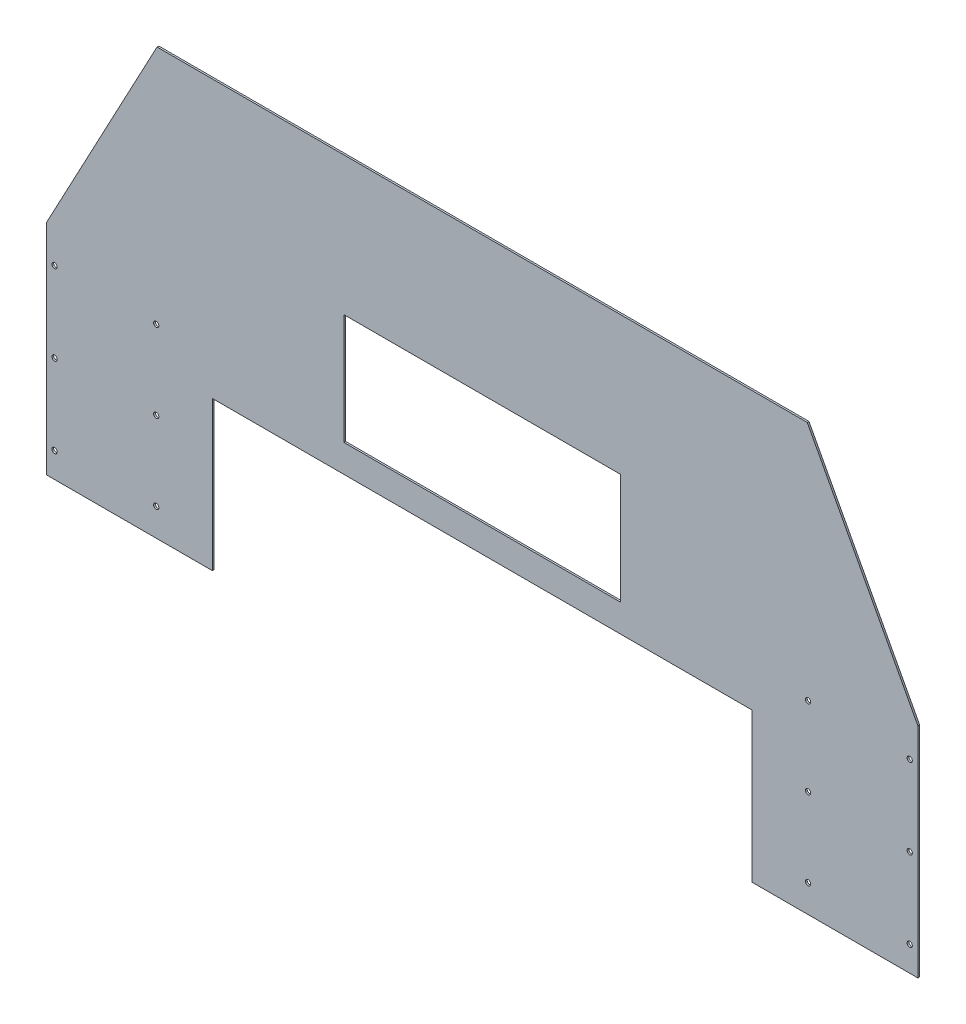
SolidWorks part; units mm, degrees
material "6061-T6 (SS)"
ref_plane "Front Plane" through (0, 0, 0) normal (0, 0, 1) x (1, 0, 0)
ref_plane "Top Plane" through (0, 0, 0) normal (0, 1, 0) x (1, 0, 0)
ref_plane "Right Plane" through (0, 0, 0) normal (1, 0, 0) x (0, 0, -1)
sketch "Sketch1" plane through (0, 0, 0) normal (0, 0, 1) x (1, 0, 0)
  line L0 (76.2, 100.203) -> (571.5, 100.203) construction
  line L1 (-76.2, -100.203) -> (76.2, -100.203)
  line L2 (-76.2, -100.203) -> (-76.2, 100.203)
  line L3 (-76.2, 100.203) -> (76.2, 100.203) construction
  line L4 (76.2, -100.203) -> (76.2, 36.703)
  line L5 (-76.2, -100.203) -> (76.2, 100.203) construction
  line L6 (-76.2, 100.203) -> (76.2, -100.203) construction
  line L7 (76.2, 36.703) -> (571.5, 36.703)
  line L8 (723.9, 100.203) -> (622.3, 290.703)
  line L9 (571.5, 100.203) -> (723.9, 100.203) construction
  line L10 (571.5, 36.703) -> (571.5, -100.203)
  line L11 (571.5, -100.203) -> (723.9, -100.203)
  line L12 (723.9, 100.203) -> (723.9, -100.203)
  line L13 (571.5, 100.203) -> (723.9, -100.203) construction
  line L14 (571.5, -100.203) -> (723.9, 100.203) construction
  line L15 (622.3, 290.703) -> (25.4, 290.703)
  line L16 (25.4, 290.703) -> (-76.2, 100.203)
  point P0 (0, 0)
  point P9 (647.7, 0)
  dimension "D1" = 200.406
  dimension "D2" = 190.5
  dimension "D3" = 63.5
  dimension "D4" = 800.1
  dimension "D5" = 152.4
  dimension "D6" = 101.6
base flange "Base-Flange1" sketch "Sketch1" thickness 1.6002 reverse thickness direction no parameters "D1"=0.7366
sketch "Sketch2" plane through (0, 0, 0) normal (0, 0, 1) x (1, 0, 0)
  circle A0 centre (24.638, 69.8754) radius 2.413
  circle A1 centre (-68.6816, 69.8754) radius 2.413
  circle A2 centre (24.638, -2.4638) radius 2.413
  circle A3 centre (-68.6816, -3.6322) radius 2.413
  circle A4 centre (-68.6816, -77.1398) radius 2.413
  circle A5 centre (24.638, -74.803) radius 2.413
  dimension "D1" = 4.826
extrude "Cut-Extrude1" cut sketch "Sketch2" against normal through all normal cut yes
ref_plane "Plane1" through (323.85, 0, 0) normal (-1, 0, 0) x (0, 0, 1)
mirror "Mirror1" about plane through (323.85, 0, 0) normal (-1, 0, 0) of "Cut-Extrude1"
sketch "Sketch3" plane through (0, 0, -1.6002) normal (0, 0, -1) x (-1, 0, 0)
  line L1 (-450.85, 163.703) -> (-196.85, 163.703)
  line L2 (-450.85, 163.703) -> (-450.85, 62.103)
  line L3 (-450.85, 62.103) -> (-196.85, 62.103)
  line L4 (-196.85, 163.703) -> (-196.85, 62.103)
  line L5 (-450.85, 163.703) -> (-196.85, 62.103) construction
  line L6 (-450.85, 62.103) -> (-196.85, 163.703) construction
  line L7 (-76.2, 36.703) -> (-571.5, 36.703) construction
  line L8 (-323.85, 112.903) -> (-323.85, 36.703) construction
  point P0 (-323.85, 112.903)
  dimension "D1" = 254
  dimension "D2" = 25.4
  dimension "D3" = 101.6
extrude "Cut-Extrude2" cut sketch "Sketch3" against normal through all normal cut yes
sketch "Bend-Lines1" [suppressed] plane through (0, 0, 0) normal (0, 1, 0) x (1, 0, 0)
sketch "Bounding-Box1" [suppressed] plane through (0, 0, 0) normal (0, 1, 0) x (1, 0, 0)
sheet metal parameters "Sheet-Metal1" thickness 1.6002 parameters "D1"=0.7366
flat pattern "Flat-Pattern1" [suppressed]
sketch "Bend-Lines2" plane through (0, 0, 0) normal (0, 1, 0) x (1, 0, 0)
sketch3d "Bounding-Box2" [suppressed]
  line L0 (51.8414, 98.1145, 0) -> (51.8414, -98.1145, 0) construction
  line L1 (-51.8414, 98.1145, 0) -> (-51.8414, -98.1145, 0) construction
  line L2 (51.8414, 98.1145, 0) -> (-51.8414, 98.1145, 0) construction
  line L3 (51.8414, -98.1145, 0) -> (-51.8414, -98.1145, 0) construction
sheet metal parameters "Sheet-Metal3" thickness 1.6002 parameters "D1"=0.7366
flat pattern "Flat-Pattern1"
sketch "Bend-Lines2" plane through (0, 0, 0) normal (0, 1, 0) x (1, 0, 0)
sketch3d "Bounding-Box2" [suppressed]
  line L0 (-54.229, -98.1145, 0) -> (745.871, -98.1145, 0) construction
  line L1 (-54.229, 98.1145, 0) -> (745.871, 98.1145, 0) construction
  line L2 (-54.229, -98.1145, 0) -> (-54.229, 98.1145, 0) construction
  line L3 (745.871, -98.1145, 0) -> (745.871, 98.1145, 0) construction
sheet metal parameters "Sheet-Metal4" thickness 1.6002 parameters "D1"=0.7366
flat pattern "Flat-Pattern1"
sketch "Bend-Lines2" plane through (0, 0, 0) normal (0, 1, 0) x (1, 0, 0)
sketch3d "Bounding-Box2" [suppressed]
  line L0 (-76.2, -100.203, 0) -> (723.9, -100.203, 0) construction
  line L1 (-76.2, 290.703, 0) -> (723.9, 290.703, 0) construction
  line L2 (-76.2, -100.203, 0) -> (-76.2, 290.703, 0) construction
  line L3 (723.9, -100.203, 0) -> (723.9, 290.703, 0) construction
sheet metal parameters "Sheet-Metal5" thickness 1.6002 parameters "D1"=0.7366
flat pattern "Flat-Pattern1"
sketch "Bend-Lines2" plane through (0, 0, 0) normal (0, 1, 0) x (1, 0, 0)
sketch3d "Bounding-Box2" [suppressed]
  line L0 (-76.2, -100.203, 0) -> (723.9, -100.203, 0) construction
  line L1 (-76.2, 290.703, 0) -> (723.9, 290.703, 0) construction
  line L2 (-76.2, -100.203, 0) -> (-76.2, 290.703, 0) construction
  line L3 (723.9, -100.203, 0) -> (723.9, 290.703, 0) construction
